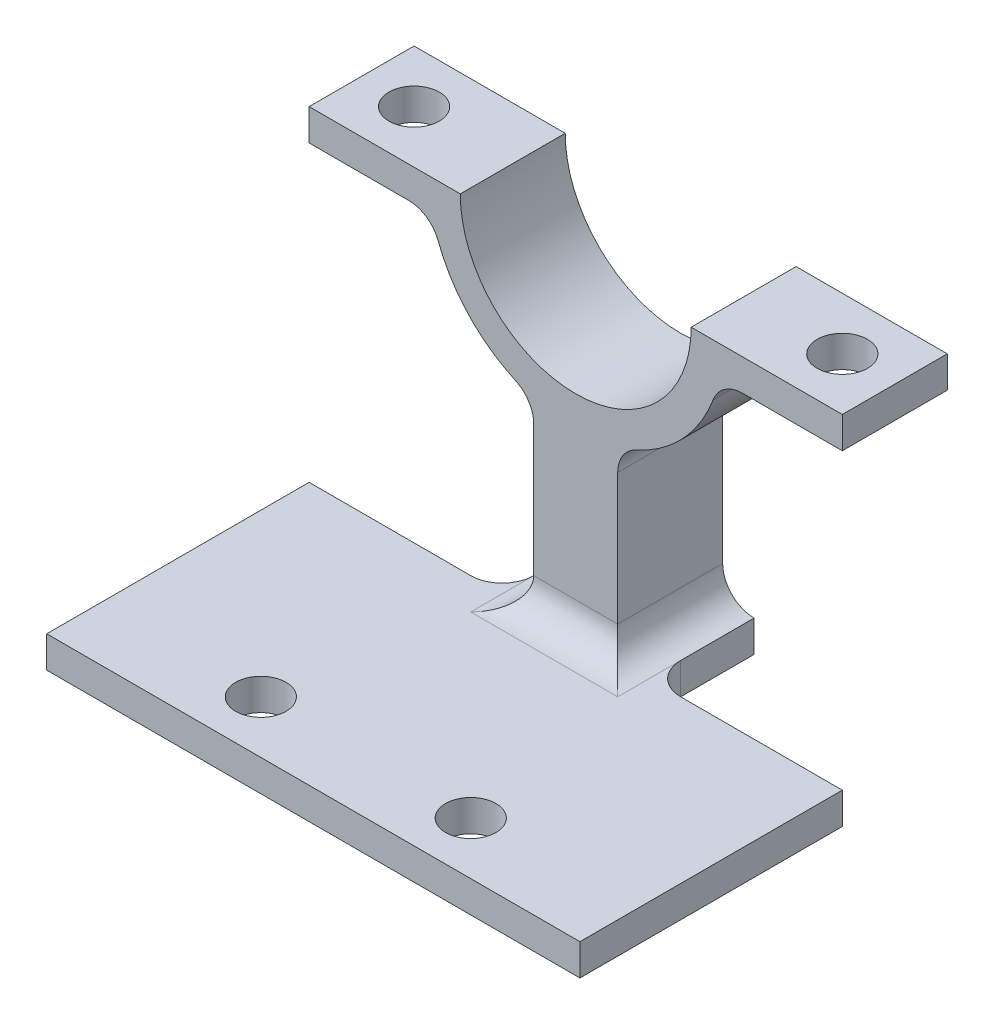
SolidWorks part; units mm, degrees
material "Windform GT"
ref_plane "Front Plane" through (0, 0, 0) normal (0, 0, 1) x (1, 0, 0)
ref_plane "Top Plane" through (0, 0, 0) normal (0, 1, 0) x (1, 0, 0)
ref_plane "Right Plane" through (0, 0, 0) normal (1, 0, 0) x (0, 0, -1)
sketch "Sketch1" plane through (0, 0, 0) normal (0, 0, 1) x (1, 0, 0)
  line L0 (5.5, 0) -> (12.7, 0)
  line L1 (12.7, 0) -> (12.7, -1.5)
  line L2 (12.7, -1.5) -> (6.8374, -1.5)
  line L5 (0, 0) -> (0, -7) construction
  line L7 (-12.7, -1.5) -> (-6.8374, -1.5)
  line L8 (-12.7, 0) -> (-12.7, -1.5)
  line L9 (-5.5, 0) -> (-12.7, 0)
  arc A2 (5.5, 0) -> (-5.5, 0) centre (0, 0) cw
  arc A3 (-6.8374, -1.5) -> (6.8374, -1.5) centre (0, 0) ccw
  point P2 (-6.3246, -1.7688)
  point P3 (0, -6.5)
  dimension "D1" = 7
  dimension "D2" = 5.5
  dimension "D3" = 12.7
  dimension "D4" = 1.5
extrude "Boss-Extrude1" add sketch "Sketch1" along normal mid plane 5
sketch "Sketch2" plane through (0, 0, 0) normal (0, 1, 0) x (1, 0, 0)
  line L0 (12.7, 0) -> (-12.7, 0) construction
  line L1 (-12.7, -2.5) -> (-12.7, 2.5) construction
  line L2 (0, 0) -> (0, 2.5) construction
  line L3 (5.5, 2.5) -> (-5.5, 2.5) construction
  circle A0 centre (-10.2, 0) radius 1.2
  circle A1 centre (10.2, 0) radius 1.2
  dimension "D1" = 2.5
  dimension "D2" = 2.4
extrude "Cut-Extrude1" cut sketch "Sketch2" against normal through all
sketch "Sketch3" plane through (0, 0, 0) normal (0, 1, 0) x (1, 0, 0)
  line L0 (5.5, -2.5) -> (5.5, 2.5) construction
  line L1 (-2, -2.5) -> (2, -2.5)
  line L2 (-2, -2.5) -> (-2, 2.5)
  line L3 (-2, 2.5) -> (2, 2.5)
  line L4 (2, -2.5) -> (2, 2.5)
  line L5 (-2, -2.5) -> (2, 2.5) construction
  line L6 (-2, 2.5) -> (2, -2.5) construction
  point P0 (0, 0)
  dimension "D1" = 4
extrude "Boss-Extrude2" add sketch "Sketch3" along normal up to surface (8.7918 mm away) from offset 15.5 up to face at (0, -4.25, 0) offset against normal yes
sketch "Sketch4" plane through (0, -15.5, 0) normal (0, -1, 0) x (1, 0, 0)
  line L0 (0, 0) -> (0, 15) construction
  line L6 (0, 0) -> (0, -2.5) construction
  line L7 (2, -2.5) -> (-2, -2.5) construction
  line L12 (3.5, -2.5) -> (-3.5, -2.5)
  line L13 (-3.5, -2.5) -> (-3.5, 2.5)
  line L18 (-2, 2.5) -> (-6.8374, 2.5) construction
  line L19 (-3.5, 2.5) -> (-12.7, 2.5)
  line L22 (-12.7, 2.5) -> (-12.7, 15)
  line L23 (-12.7, 15) -> (12.7, 15)
  line L24 (12.7, 2.5) -> (12.7, 15)
  line L25 (3.5, 2.5) -> (12.7, 2.5)
  line L26 (3.5, -2.5) -> (3.5, 2.5)
  dimension "D1" = 7
  dimension "D2" = 12.5
extrude "Boss-Extrude3" add sketch "Sketch4" along normal blind 1.5
fillet "Fillet1" radius 1.5 9 edges at (-3.5, -16.25, 2.5) (3.5, -16.25, 2.5) (2, -15.5, 0) (2, -6.7082, 0) (6.8374, -1.5, 0) (-6.8374, -1.5, 0) (-2, -6.7082, 0) (-2, -15.5, 0) (0, -15.5, 2.5)
sketch "Sketch5" plane through (0, 0, 0) normal (0, 1, 0) x (1, 0, 0)
  line L0 (-5, 2.5) -> (-5, -15) construction
  line L1 (12.7, -15) -> (-12.7, -15) construction
  line L2 (0, 2.5) -> (0, -15) construction
  line L3 (5, 2.5) -> (5, -15) construction
  line L4 (5.5, 2.5) -> (-5.5, 2.5) construction
  line L5 (-5.5, 2.5) -> (-12.7, 2.5) construction
  circle A0 centre (-5, -12.5) radius 1.2
  circle A3 centre (5, -12.5) radius 1.2
  point P18 (0, 0)
  point P19 (0, -8.8323)
  point P20 (0, 0)
  point P21 (-7.6137, 2.5)
  dimension "D2" = 2.4
  dimension "D1" = 2.5
  dimension "D4" = 5
extrude "Cut-Extrude2" cut sketch "Sketch5" against normal through all
